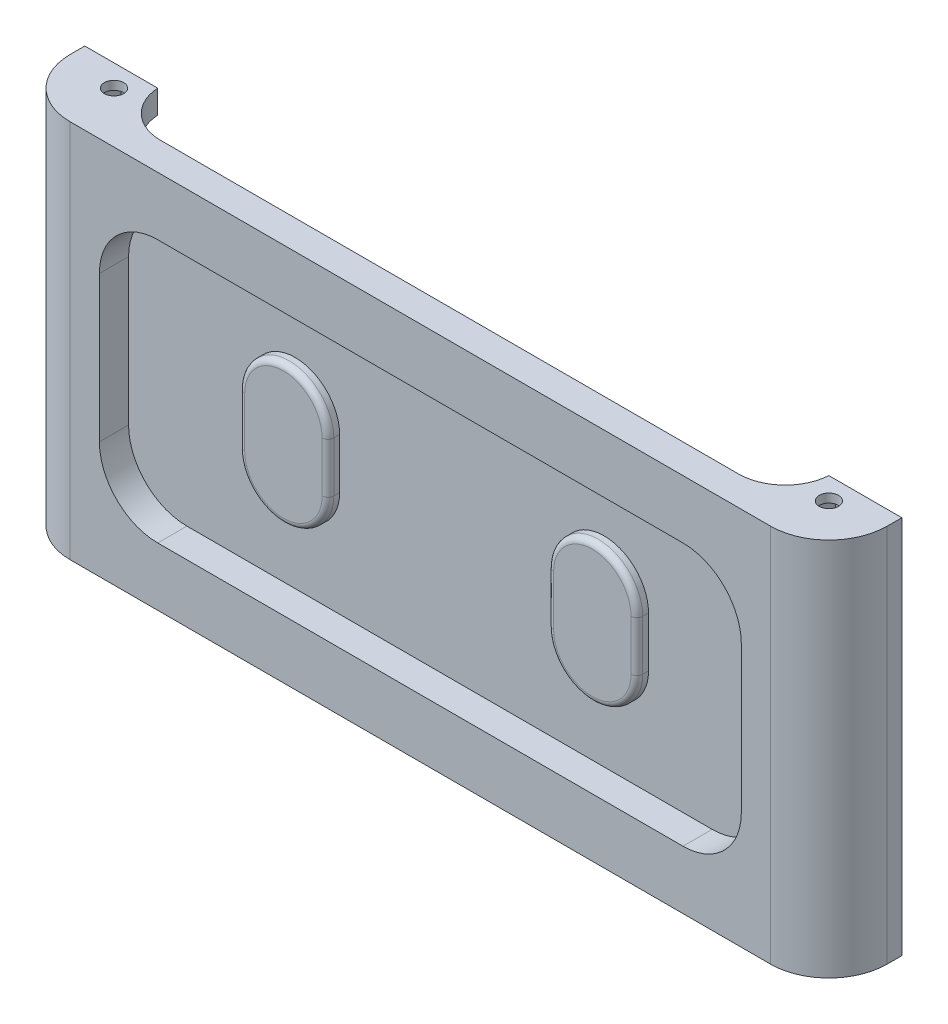
SolidWorks part; units mm, degrees
ref_plane "Front Plane" through (0, 0, 0) normal (0, 0, 1) x (1, 0, 0)
ref_plane "Top Plane" through (0, 0, 0) normal (0, 1, 0) x (1, 0, 0)
ref_plane "Right Plane" through (0, 0, 0) normal (1, 0, 0) x (0, 0, -1)
sketch "Sketch1" plane through (0, 0, 0) normal (0, 0, 1) x (1, 0, 0)
  line L1 (0, 0) -> (140, 0)
  line L2 (0, 0) -> (0, 65)
  line L3 (0, 65) -> (140, 65)
  line L4 (140, 0) -> (140, 65)
  dimension "D1" = 140
  dimension "D2" = 65
extrude "Boss-Extrude1" add sketch "Sketch1" along normal blind 12.5
sketch "Sketch4" plane through (0, 65, 0) normal (0, 1, 0) x (1, 0, 0)
  line L6 (5, 0) -> (135, 0)
  line L9 (135, 0) -> (135, -7.5)
  line L10 (5, -7.5) -> (5, 0)
  line L11 (135, -7.5) -> (5, -7.5)
  line L12 (135, 0) -> (135, -7.5)
  line L13 (5, -7.5) -> (5, 0)
  line L14 (135, -7.5) -> (5, -7.5)
  dimension "D1" = 5
extrude "Cut-Extrude3" cut sketch "Sketch4" against normal through all
sketch "Sketch2" plane through (0, 0, 12.5) normal (0, 0, 1) x (1, 0, 0)
  line L0 (70, 65) -> (70, 0) construction
  line L1 (140, 65) -> (0, 65) construction
  line L2 (0, 0) -> (140, 0) construction
  line L3 (140, 0) -> (140, 65) construction
  line L4 (15, 55) -> (125, 55)
  line L5 (15, 55) -> (15, 10)
  line L6 (15, 10) -> (125, 10)
  line L7 (125, 55) -> (125, 10)
  line L8 (15, 55) -> (125, 10) construction
  line L9 (15, 10) -> (125, 55) construction
  point P6 (70, 32.5)
  dimension "D1" = 15
  dimension "D2" = 10
extrude "Cut-Extrude1" cut sketch "Sketch2" against normal through all
fillet "Fillet1" radius 10 4 edges at (15, 10, 10) (15, 55, 10) (125, 10, 10) (125, 55, 10)
fillet "Fillet2" radius 10 2 edges at (140, 32.5, 12.5) (0, 32.5, 12.5)
sketch "Sketch5" plane through (0, 0, 0) normal (0, -1, 0) x (1, 0, 0)
  line L0 (0, 0) -> (5, 0) construction
  line L1 (5, 7.5) -> (12.5, 7.5)
  line L2 (5, 7.5) -> (5, 0)
  line L3 (5, 0) -> (12.5, 0)
  line L4 (12.5, 7.5) -> (12.5, 0)
  line L5 (135, 7.5) -> (127.5, 7.5)
  line L6 (135, 7.5) -> (135, 0)
  line L7 (135, 0) -> (127.5, 0)
  line L8 (127.5, 7.5) -> (127.5, 0)
extrude "Boss-Extrude2" add sketch "Sketch5" against normal blind 4
sketch "Sketch6" plane through (0, 4, 0) normal (0, 1, 0) x (1, 0, 0)
  line L0 (8.75, 0) -> (8.75, -7.5) construction
  line L1 (11.9254, -3.75) -> (10.3377, -1)
  line L2 (10.3377, -1) -> (7.1623, -1)
  line L3 (7.1623, -1) -> (5.5746, -3.75)
  line L4 (5.5746, -3.75) -> (7.1623, -6.5)
  line L5 (7.1623, -6.5) -> (10.3377, -6.5)
  line L6 (10.3377, -6.5) -> (11.9254, -3.75)
  line L7 (5, 0) -> (12.5, 0) construction
  line L8 (12.5, -7.5) -> (5, -7.5) construction
  line L9 (70, -12.5) -> (70, 1.5241) construction
  line L10 (130, -12.5) -> (10, -12.5) construction
  line L11 (134.4254, -3.75) -> (132.8377, -6.5)
  line L12 (132.8377, -6.5) -> (129.6623, -6.5)
  line L13 (129.6623, -6.5) -> (128.0746, -3.75)
  line L14 (128.0746, -3.75) -> (129.6623, -1)
  line L15 (129.6623, -1) -> (132.8377, -1)
  line L16 (132.8377, -1) -> (134.4254, -3.75)
  circle A0 centre (8.75, -3.75) radius 2.75 construction
  circle A1 centre (8.75, -3.75) radius 1.65
  circle A2 centre (131.25, -3.75) radius 1.65
  dimension "D1" = 3.3
  dimension "D2" = 5.5
extrude "Cut-Extrude5" cut sketch "Sketch6<2>" against normal through all contours A1 | A2 region at (8.75, 4, 3.75) region at (131.25, 4, 3.75)
sketch "Sketch6<2>" plane through (0, 4, 0) normal (0, 1, 0) x (1, 0, 0) same geometry as "Sketch6"
extrude "Cut-Extrude4" cut sketch "Sketch6" against normal blind 2.5
fillet "Fillet3" radius 8 2 edges at (127.5, 2, 7.5) (12.5, 2, 7.5)
ref_plane "Plane1" through (0, 32.5, 0) normal (0, 1, 0) x (1, 0, 0)
mirror "Mirror1" about plane through (0, 32.5, 0) normal (0, 1, 0) of "Cut-Extrude5", "Cut-Extrude4", "Boss-Extrude2", "Fillet3"
sketch "Sketch7" plane through (0, 0, 7.5) normal (0, 0, -1) x (-1, 0, 0)
  line L1 (-135, 61) -> (-5, 61)
  line L2 (-135, 61) -> (-135, 4)
  line L3 (-135, 4) -> (-5, 4)
  line L4 (-5, 61) -> (-5, 4)
extrude "Boss-Extrude3" add sketch "Sketch7" along normal blind 1 separate body
sketch "Sketch8" plane through (0, 0, 7.5) normal (0, 0, 1) x (1, 0, 0)
  line L0 (70, 55) -> (70, 24.7719) construction
  line L1 (115, 55) -> (25, 55) construction
  line L2 (25, 10) -> (115, 10) construction
  line L3 (43.5327, 36.6686) -> (96.4673, 36.6686) construction
  line L5 (70, 19.7719) -> (70, 10) construction
  line L6 (43.5327, 28.0667) -> (96.4673, 28.0667) construction
  line L7 (35.901, 36.6686) -> (35.901, 28.0667)
  line L8 (51.1643, 36.6686) -> (51.1643, 28.0667)
  line L9 (88.8357, 36.6686) -> (88.8357, 28.0667)
  line L10 (104.099, 36.6686) -> (104.099, 28.0667)
  arc A0 (51.1643, 36.6686) -> (35.901, 36.6686) centre (43.5327, 36.6686) ccw
  arc A1 (104.099, 36.6686) -> (88.8357, 36.6686) centre (96.4673, 36.6686) ccw
  arc A2 (35.901, 28.0667) -> (51.1643, 28.0667) centre (43.5327, 28.0667) ccw
  arc A3 (88.8357, 28.0667) -> (104.099, 28.0667) centre (96.4673, 28.0667) ccw
  point P8 (0, 0)
  point P9 (0, 0)
  point P11 (70, 36.6686)
  point P13 (92.6296, 36.6686)
  point P14 (93.1589, 28.0667)
  point P24 (96.4673, 36.6686)
extrude "Boss-Extrude4" add sketch "Sketch8" along normal blind 2 separate body contours A0 | A1 region at (43.5327, 32.3677, 7.5) region at (96.4673, 32.3677, 7.5)
sketch "Sketch9" plane through (0, 0, 6.5) normal (0, 0, -1) x (-1, 0, 0)
  line L0 (-19, 0) -> (-19, 42.7) construction
  line L1 (-20.4844, 0) -> (-119.5156, 0) construction
  line L2 (0, 0) -> (-19, 0) construction
  line L3 (-70, 65) -> (-70, 0) construction
  line L4 (-20.4844, 65) -> (-119.5156, 65) construction
  circle A0 centre (-19, 42.7) radius 8.4
  circle A1 centre (-121, 42.7) radius 8.4
  dimension "D3" = 16.8
  dimension "D1" = 19
  dimension "D2" = 42.7
extrude "Boss-Extrude6" add sketch "Sketch9" along normal blind 10 separate body
combine bodies "Combine1" operation type add bodies to combine 116 110 117
chamfer "Chamfer1" distance 3 angle 45 2 edges at (10.6, 42.7, 6.5) (112.6, 42.7, 6.5)
fillet "Fillet5" radius 1 2 edges at (10.6, 42.7, -3.5) (129.4, 42.7, -3.5)
fillet "Fillet6" radius 1 4 edges at (96.4673, 44.3003, 9.5) (104.099, 32.3677, 9.5) (96.4673, 20.4351, 9.5) (88.8357, 32.3677, 9.5)
fillet "Fillet7" radius 1 4 edges at (43.5327, 44.3003, 9.5) (51.1643, 32.3677, 9.5) (43.5327, 20.4351, 9.5) (35.901, 32.3677, 9.5)
